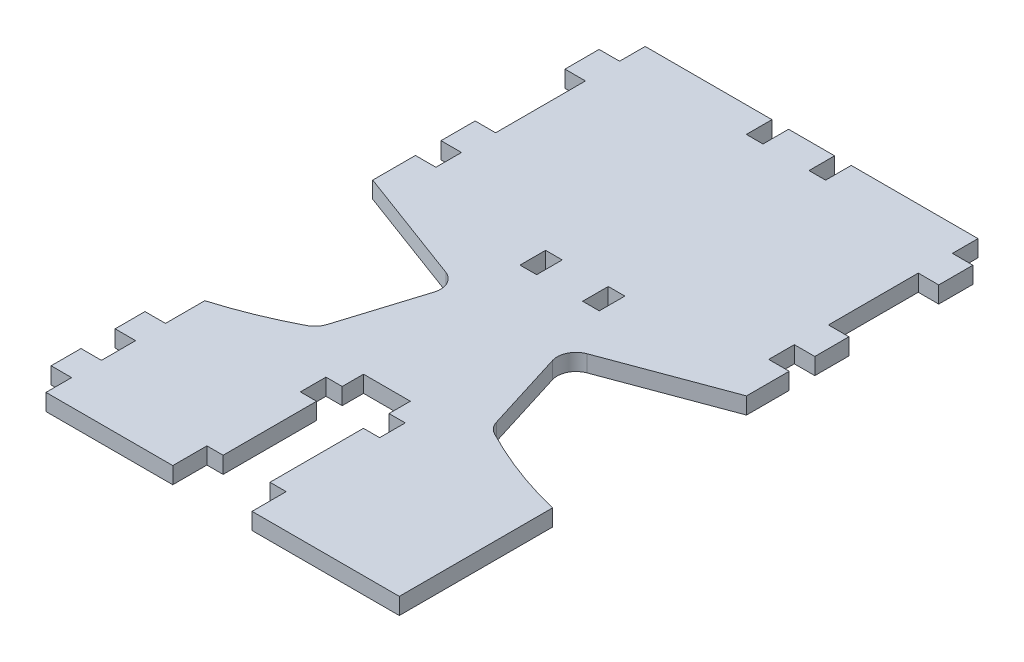
SolidWorks part; units mm, degrees
ref_plane "Front" through (0, 0, 0) normal (0, 0, 1) x (1, 0, 0)
ref_plane "Top" through (0, 0, 0) normal (0, 1, 0) x (1, 0, 0)
ref_plane "Right" through (0, 0, 0) normal (1, 0, 0) x (0, 0, -1)
ref_axis "side-side" through (80.9, 0, 0) along (-1, 0, 0)
ref_axis "up-down" through (0, 50, 0) along (0, -1, 0)
ref_axis "front-back" through (0, 0, -80.9) along (0, 0, 1)
sketch "Sketch1" plane through (0, 0, 0) normal (0, 1, 0) x (1, 0, 0)
  line L0 (0, 45.72) -> (0, 82.7528) construction
  line L1 (-49.53, 45.72) -> (-11.7983, 45.72)
  line L2 (-55.626, 38.1) -> (-55.626, 27.94)
  line L3 (-49.53, -132.6173) -> (-11.7983, -132.6173)
  line L4 (55.626, 38.1) -> (55.626, 27.94)
  line L5 (11.7983, -122.4573) -> (11.7983, -94.6424) construction
  line L6 (11.7983, -132.6173) -> (55.626, -132.6173)
  line L7 (6.9723, -122.4573) -> (11.7983, -122.4573)
  line L8 (-17.632, -49.0369) -> (-25.1877, -73.287)
  line L9 (-21.0198, -42.1368) -> (-55.626, -29.2719)
  line L10 (-55.626, -97.0573) -> (-55.626, -105.9473)
  line L11 (55.626, -29.2719) -> (21.0198, -42.1368)
  line L12 (17.632, -49.0369) -> (25.1877, -73.287)
  line L13 (55.626, -87.0224) -> (55.626, -132.6173)
  line L14 (55.626, -16.5719) -> (55.626, -29.2719)
  line L15 (-49.53, 38.1) -> (-55.626, 38.1)
  line L16 (-49.53, 38.1) -> (-49.53, 45.72)
  line L17 (-55.626, -16.5719) -> (-55.626, -29.2719)
  line L18 (-55.626, 1.2081) -> (-55.626, -8.9519)
  line L19 (-49.53, -8.9519) -> (-55.626, -8.9519)
  line L20 (-49.53, -8.9519) -> (-49.53, -16.5719)
  line L21 (-49.53, -16.5719) -> (-55.626, -16.5719)
  line L22 (-55.626, 27.94) -> (-49.53, 27.94)
  line L23 (-57.4537, -89.4373) -> (-47.6065, -89.4373) construction
  line L24 (-11.7983, -122.4573) -> (-11.7983, -94.6424) construction
  line L25 (55.626, 38.1) -> (49.53, 38.1)
  line L26 (49.53, 45.72) -> (49.53, 38.1)
  line L27 (55.626, -16.5719) -> (49.53, -16.5719)
  line L29 (55.626, -8.9519) -> (49.53, -8.9519)
  line L30 (49.53, -16.5719) -> (49.53, -8.9519)
  line L31 (-55.626, -124.9973) -> (-49.53, -124.9973)
  line L32 (-49.53, -132.6173) -> (-49.53, -124.9973)
  line L33 (-6.9723, -94.6424) -> (-6.9723, -122.4573)
  line L34 (6.9723, -94.6424) -> (6.9723, -122.4573)
  line L36 (6.9723, -94.6424) -> (11.7983, -94.6424)
  line L37 (-11.7983, -87.0224) -> (-6.9723, -87.0224)
  line L38 (-11.7983, -87.0224) -> (-11.7983, -94.6424)
  line L39 (-55.626, -97.0573) -> (-49.53, -97.0573)
  line L40 (-49.53, -85.3598) -> (-49.53, -97.0573)
  line L41 (-11.7983, -94.6424) -> (-6.9723, -94.6424)
  line L42 (11.7983, -87.0224) -> (11.7983, -94.6424)
  line L43 (11.7983, 45.72) -> (49.53, 45.72)
  line L44 (-11.7983, -132.6173) -> (-11.7983, -122.4573)
  line L45 (-11.7983, -122.4573) -> (-6.9723, -122.4573)
  line L46 (11.7983, -132.6173) -> (11.7983, -122.4573)
  line L47 (-6.8453, 45.72) -> (6.8453, 45.72)
  line L48 (-11.7983, 45.72) -> (-11.7983, 38.1)
  line L49 (-11.7983, 38.1) -> (-6.8453, 38.1)
  line L50 (-6.8453, 45.72) -> (-6.8453, 38.1)
  line L52 (6.8453, 45.72) -> (6.8453, 38.1)
  line L53 (6.8453, 38.1) -> (11.7983, 38.1)
  line L54 (11.7983, 45.72) -> (11.7983, 38.1)
  line L55 (11.7983, -21.6519) -> (6.8453, -21.6519)
  line L56 (11.7983, -21.6519) -> (11.7983, -29.2719)
  line L57 (11.7983, -29.2719) -> (6.8453, -29.2719)
  line L58 (6.8453, -21.6519) -> (6.8453, -29.2719)
  line L59 (-11.7983, -21.6519) -> (-6.8453, -21.6519)
  line L60 (-11.7983, -21.6519) -> (-11.7983, -29.2719)
  line L61 (-11.7983, -29.2719) -> (-6.8453, -29.2719)
  line L62 (-6.8453, -21.6519) -> (-6.8453, -29.2719)
  line L64 (-6.9723, -87.0224) -> (-6.9723, -80.6724)
  line L65 (-6.9723, -80.6724) -> (6.9723, -80.6724)
  line L66 (6.9723, -87.0224) -> (6.9723, -80.6724)
  line L68 (6.9723, -87.0224) -> (11.7983, -87.0224)
  line L70 (55.626, 1.2081) -> (55.626, -8.9519)
  line L71 (-55.626, 1.2081) -> (-49.53, 1.2081)
  line L72 (-49.53, 27.94) -> (-49.53, 1.2081)
  line L73 (55.626, 27.94) -> (49.53, 27.94)
  line L74 (-55.626, -116.1073) -> (-55.626, -124.9973)
  line L75 (55.626, 1.2081) -> (49.53, 1.2081)
  line L76 (49.53, 27.94) -> (49.53, 1.2081)
  line L77 (-55.626, -105.9473) -> (-49.53, -105.9473)
  line L79 (-55.626, -116.1073) -> (-49.53, -116.1073)
  line L80 (-49.53, -105.9473) -> (-49.53, -116.1073)
  arc A1 (-17.632, -49.0369) -> (-21.0198, -42.1368) centre (-22.967, -47.3746) ccw
  arc A2 (-27.9391, -76.5796) -> (-25.1877, -73.287) centre (-30.5228, -71.6248) ccw
  arc A3 (-27.9391, -76.5796) -> (-49.53, -85.3598) centre (-85.09, 33.02) cw
  arc A4 (21.0198, -42.1368) -> (17.632, -49.0369) centre (22.967, -47.3746) ccw
  arc A5 (25.1877, -73.287) -> (27.9391, -76.5796) centre (30.5228, -71.6248) ccw
  arc A6 (27.9391, -76.5796) -> (55.626, -87.0224) centre (85.09, 33.02) ccw
  dimension "D2" = 10.16
  dimension "D1" = 10.16
  dimension "D3" = 8.89
  dimension "D4" = 8.89
  dimension "D5" = 4.826
  dimension "D6" = 4.826
  dimension "D7" = 4.953
extrude "Boss-Extrude1" add sketch "Sketch1" along normal mid plane 4.953
